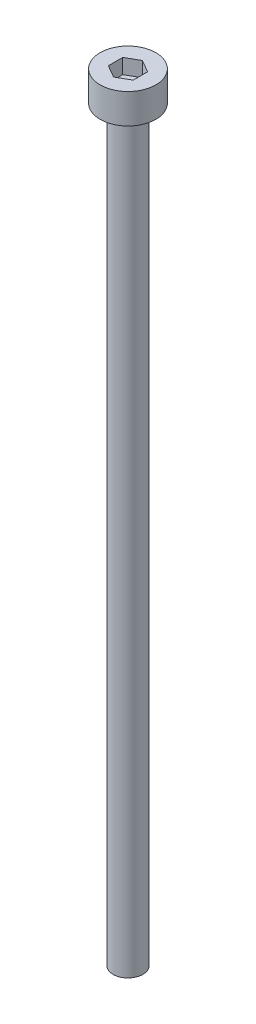
SolidWorks part; units mm, degrees
ref_plane "前视基准面" through (0, 0, 0) normal (0, 0, 1) x (1, 0, 0)
ref_plane "上视基准面" through (0, 0, 0) normal (0, 1, 0) x (1, 0, 0)
ref_plane "右视基准面" through (0, 0, 0) normal (1, 0, 0) x (0, 0, -1)
other "Configuration Table"
sketch "草图1" plane through (0, 0, 0) normal (0, 1, 0) x (1, 0, 0)
  line L1 (1.25, -0.7217) -> (1.25, 0.7217)
  line L2 (1.25, 0.7217) -> (0, 1.4434)
  line L3 (0, 1.4434) -> (-1.25, 0.7217)
  line L4 (-1.25, 0.7217) -> (-1.25, -0.7217)
  line L5 (-1.25, -0.7217) -> (0, -1.4434)
  line L6 (0, -1.4434) -> (1.25, -0.7217)
  circle A0 centre (0, 0) radius 2.8
  circle A1 centre (0, 0) radius 1.25 construction
  dimension "D1" = 5.6
  dimension "D2" = 2.5
extrude "凸台-拉伸1" add sketch "草图1" along normal blind 3
extrude "凸台-拉伸2" add sketch "草图1<2>" along normal blind 1.5 contours L5 L6 L1 L2 L3 L4 region at (0, 0, 0)
sketch "草图1<2>" plane through (0, 0, 0) normal (0, 1, 0) x (1, 0, 0) same geometry as "草图1"
sketch "草图2" plane through (0, 0, 0) normal (0, -1, 0) x (1, 0, 0)
  circle A0 centre (0, 0) radius 1.5
  dimension "D1" = 3
extrude "凸台-拉伸3" add sketch "草图2" along normal blind 75
